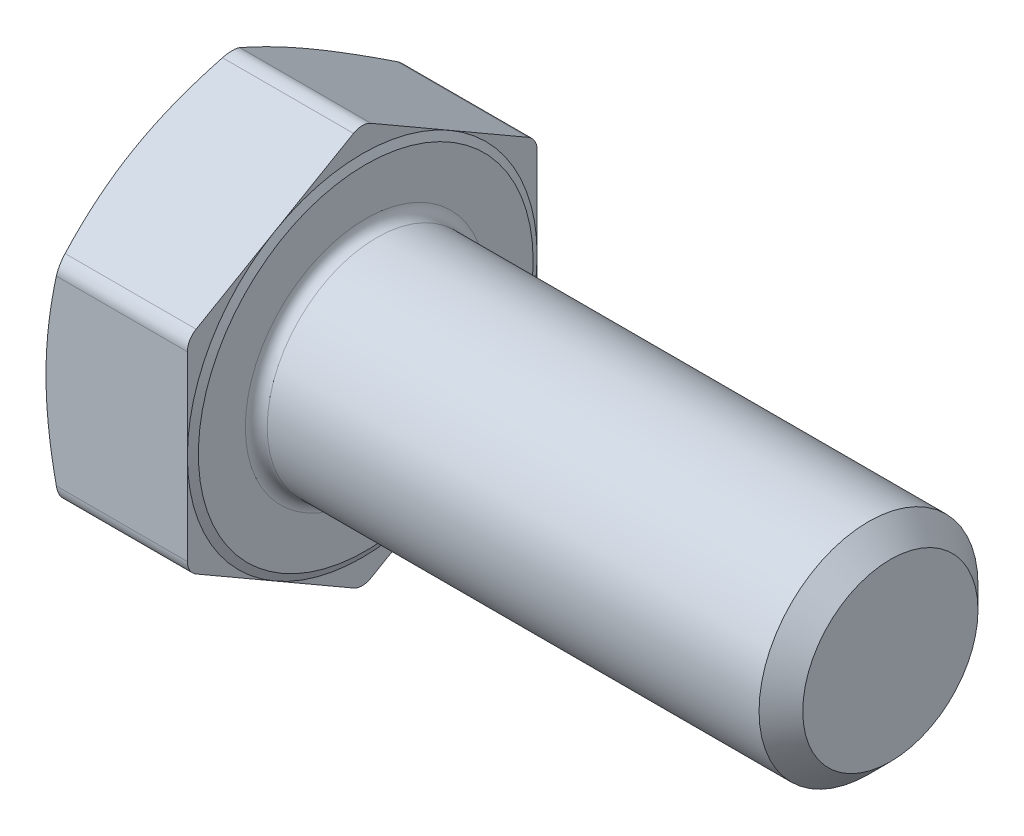
SolidWorks part; units mm, degrees
ref_plane "Front Plane" through (0, 0, 0) normal (0, 0, 1) x (1, 0, 0)
ref_plane "Top Plane" through (0, 0, 0) normal (0, 1, 0) x (1, 0, 0)
ref_plane "Right Plane" through (0, 0, 0) normal (1, 0, 0) x (0, 0, -1)
sketch "Sketch1" plane through (0, 0, 0) normal (0, 0, 1) x (1, 0, 0)
  line L0 (0, 0) -> (19.05, 0) construction
  line L1 (0, 0) -> (-5.5562, 0) construction
  line L2 (0, 6.35) -> (0, -6.35) construction
  line L3 (-5.5563, 6.35) -> (-5.5562, -6.35) construction
  line L4 (19.05, 3.9751) -> (19.05, -3.9751) construction
  line L8 (17.9917, 3.9751) -> (19.05, 3.9751) construction
  point P8 (17.9917, 0)
  point P11 (15.3458, -3.9751)
  point P12 (1.0583, 0)
  dimension "Head Height" = 5.5562
  dimension "Head Width" = 12.7
  dimension "Length" = 19.05
  dimension "Thread Size" = 7.9502
  dimension "D1" = 3.7042
  dimension "Thread Pitch" = 1.0583
  dimension "D2" = 1.0583
sketch "Sketch2" plane through (0, 0, 0) normal (1, 0, 0) x (0, 0, -1)
  circle A0 centre (0, 0) radius 3.9751
extrude "Boss-Extrude1" add sketch "Sketch2" along normal up to vertex (19.05 mm away) up to point (19.05, 3.9751, 0)
sketch "Sketch3" plane through (0, 0, 0) normal (-1, 0, 0) x (0, 0, 1)
  line L0 (0, 7.3323) -> (0, 0) construction
  line L1 (0, 7.3323) -> (-6.35, 3.6662)
  line L2 (-6.35, 3.6662) -> (-6.35, -3.6662)
  line L3 (-6.35, -3.6662) -> (0, -7.3323)
  line L4 (0, -7.3323) -> (6.35, -3.6662)
  line L5 (6.35, -3.6662) -> (6.35, 3.6662)
  line L6 (6.35, 3.6662) -> (0, 7.3323)
  circle A0 centre (0, 0) radius 6.35 construction
extrude "Boss-Extrude2" add sketch "Sketch3" along normal up to vertex (5.5563 mm away) up to point (-5.5563, 6.35, 0)
sketch "Sketch5" plane through (-5.5563, 0, 0) normal (-1, 0, 0) x (0, 0, 1)
  circle A0 centre (0, 0) radius 6.35 construction
  circle A1 centre (0, 0) radius 6.35 construction
  circle A2 centre (0, 0) radius 5.715
  dimension "D1" = 0.635
extrude "Cut-Extrude1" cut sketch "Sketch5" against normal up to vertex (5.5563 mm away) draft 65 flip side to cut up to point (0, 0, 0)
sketch "Sketch11" plane through (-5.5563, 0, 0) normal (-1, 0, 0) x (0, 0, 1)
  line L0 (0, 4.5085) -> (0, 2.794) construction
  line L1 (0.254, 4.5085) -> (0.254, 2.794)
  line L2 (-0.254, 4.5085) -> (-0.254, 2.794)
  arc A0 (0.254, 4.5085) -> (-0.254, 4.5085) centre (0, 4.5085) ccw
  arc A1 (-0.254, 2.794) -> (0.254, 2.794) centre (0, 2.794) ccw
  circle A2 centre (0, 0) radius 4.7625 construction
  circle A3 centre (0, 0) radius 2.54 construction
  point P3 (0, 3.6513)
  dimension "D1" = 9.525
  dimension "D2" = 5.08
  dimension "D3" = 0.508
extrude "Boss-Extrude5" add sketch "Sketch11" along normal blind 0.0635
fillet "Fillet5" radius 0.0635 4 edges at (-5.6198, 3.6513, 0.254) (-5.6198, 2.54, 0) (-5.6198, 3.6513, -0.254) (-5.6198, 4.7625, 0)
pattern_circular "CirPattern1" count 6 over 360 about axis through (0, 0, 0) along (-1, 0, 0) of "Boss-Extrude5", "Fillet5" reverse direction yes
fillet "Fillet7" radius 0.635 6 edges at (-2.401, -7.3323, 0) (-2.401, -3.6662, -6.35) (-2.401, 3.6662, -6.35) (-2.401, 7.3323, 0) (-2.401, -3.6662, 6.35) (-2.401, 3.6662, 6.35)
chamfer "Chamfer1" distance 0.7938 angle 45 1 edges at (19.05, 0, -3.9751)
sketch "Sketch15" plane through (0, 0, 0) normal (0, 0, 1) x (1, 0, 0)
  line L0 (0, 6.0776) -> (-0.127, 6.35)
  line L1 (0, 6.35) -> (0, -6.35) construction
  line L2 (-0.127, 6.35) -> (-0.127, 7.3323)
  line L3 (-0.127, 7.3323) -> (0, 7.3323)
  line L4 (0, 7.3323) -> (0, 6.0776)
  dimension "D1" = 0.127
  dimension "D2" = 25
revolve "Cut-Revolve1" cut sketch "Sketch15" angle 360 about L1
fillet "Fillet4" radius 0.3975 1 edges at (0, 0, 3.9751)
sketch "Reference Sketch1" plane through (0, 0, 0) normal (1, 0, 0) x (0, 0, -1)
  line L1 (0, 7.3323) -> (-6.35, 3.6662)
  line L2 (-6.35, 3.6662) -> (-6.35, -3.6662)
  line L3 (-6.35, -3.6662) -> (0, -7.3323)
  line L4 (0, -7.3323) -> (6.35, -3.6662)
  line L5 (6.35, -3.6662) -> (6.35, 3.6662)
  line L6 (6.35, 3.6662) -> (0, 7.3323)
  circle A0 centre (0, 0) radius 6.35 construction
  circle A1 centre (0, 0) radius 6.35
sketch "Sketch12" [suppressed] plane through (19.05, 0, 0) normal (1, 0, 0) x (0, 0, -1)
  circle A1 centre (0, 0) radius 3.9751
ref_plane "Plane2" [suppressed] through (1.0583, 0, 0) normal (1, 0, 0) x (0, 0, -1)
split "Split1" [suppressed] bodies to split 126 116
curve "Helix/Spiral2" [suppressed] pitch 1.0583 height 20.1083 turns 19 parameters "Pitch"=1.0583
sketch "Sketch13" [suppressed] plane through (0, 0, 0) normal (0, 0, 1) x (1, 0, 0)
  line L0 (18.9839, 4.0897) -> (19.513, 3.1731) construction
  line L1 (19.513, 3.1731) -> (20.0422, 4.0897) construction
  line L2 (20.0422, 4.0897) -> (18.9839, 4.0897) construction
  line L3 (19.513, 3.1731) -> (19.513, 3.2877) construction
  line L4 (19.05, 3.9751) -> (19.976, 3.9751)
  line L5 (19.513, 3.9751) -> (19.513, 4.0897) construction
  line L6 (19.976, 3.9751) -> (19.5792, 3.2877)
  line L7 (19.5792, 3.2877) -> (19.4469, 3.2877)
  line L8 (19.4469, 3.2877) -> (19.05, 3.9751)
  line L9 (17.9917, 3.9751) -> (19.05, 3.9751) construction
  dimension "D1" = 0.1323
sweep "Cut-Sweep1" [suppressed] cut profiles "Sketch13" path "Helix/Spiral2"
sketch "Sketch14" [suppressed] plane through (1.0583, 0, 0) normal (1, 0, 0) x (0, 0, -1)
  circle A1 centre (0, 0) radius 3.9751
  circle A2 centre (0, 0) radius 3.9751
  dimension "D1" = 0
extrude "Boss-Extrude4" [suppressed] add sketch "Sketch14" along normal through all draft 50
equation "\"D1@Sketch11\"=\"Head Width@Sketch1\" * 0.75"
equation "\"D2@Sketch11\"=\"Head Width@Sketch1\"*0.4"
equation "\"D3@Sketch11\"=\"Head Width@Sketch1\" * .04"
equation "\"D3@Helix/Spiral2\"=\"Length@Sketch1\" + \"Thread Pitch@Sketch1\""
equation "\"D1@Chamfer1\"=\"Thread Pitch@Sketch1\"*0.750"
equation "\"D1@Sketch1\"=\"Thread Pitch@Sketch1\"*3.5"
equation "\"Pitch@Helix/Spiral2\"=\"Thread Pitch@Sketch1\""
equation "\"D1@Sketch13\"=\"Thread Pitch@Sketch1\"*0.125"
equation "\"D1@Sketch5\"=\"Head Width@Sketch1\"*0.05"
equation "\"D1@Fillet4\"=\"Thread Size@Sketch1\"*0.05"
equation "\"D2@Sketch1\"=\"Thread Pitch@Sketch1\""
equation "\"D1@Fillet7\"=\"Head Width@Sketch1\"*0.05"
